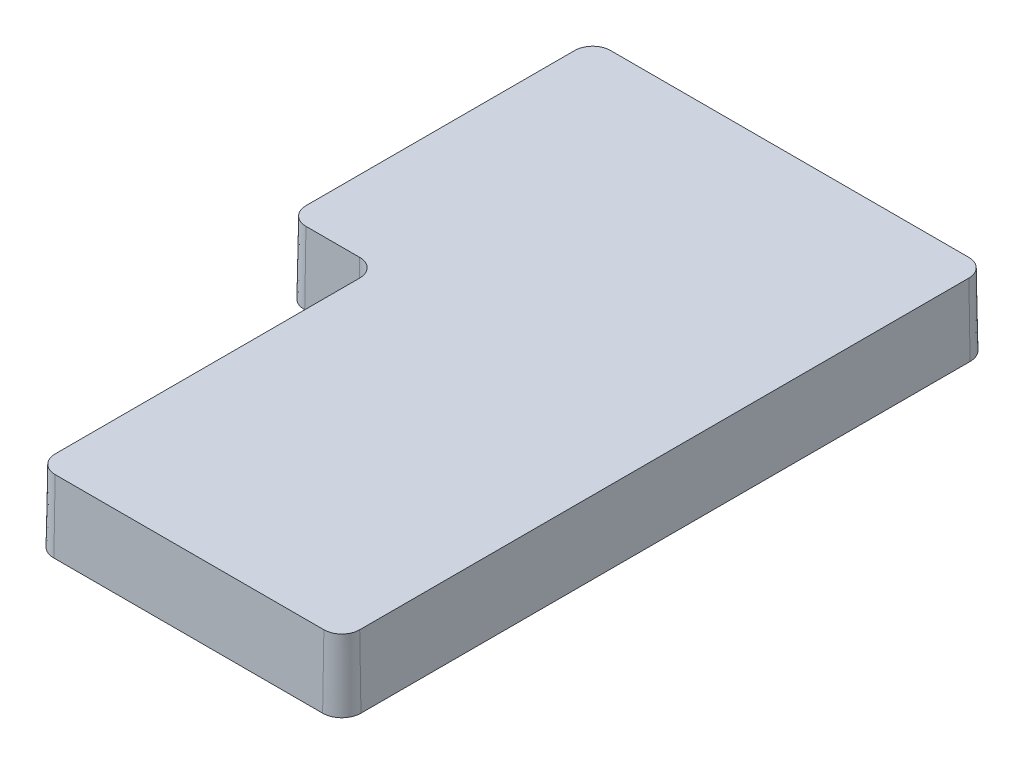
SolidWorks part; units mm, degrees
ref_plane "Front Plane" through (0, 0, 0) normal (0, 0, 1) x (1, 0, 0)
ref_plane "Top Plane" through (0, 0, 0) normal (0, 1, 0) x (1, 0, 0)
ref_plane "Right Plane" through (0, 0, 0) normal (1, 0, 0) x (0, 0, -1)
ref_plane "Right_New_Plane" through (-0.69, 0, 0) normal (1, 0, 0) x (0, 0, -1)
sketch "Sketch1" plane through (0, 0, 0) normal (0, 1, 0) x (1, 0, 0)
  line L0 (9.3071, 15.4536) -> (-10.6929, 15.4536)
  line L1 (10.3071, -19.5464) -> (10.3071, 14.4536)
  line L2 (-5.6929, -20.5464) -> (9.3071, -20.5464)
  line L3 (-6.6929, -2.5464) -> (-6.6929, -19.5464)
  line L4 (-10.6929, -1.5464) -> (-7.6929, -1.5464)
  line L5 (-11.6929, 14.4536) -> (-11.6929, -0.5464)
  line L6 (-55, 0) -> (55, 0) construction
  line L7 (0, -55) -> (0, 55) construction
  line L8 (-0.6929, 15.4536) -> (-0.69, -20.5464) construction
  line L9 (-0.69, -55) -> (-0.69, 55) construction
  line L10 (10.3071, -2.5464) -> (-6.6929, -2.5464) construction
  arc A0 (-10.6929, 15.4536) -> (-11.6929, 14.4536) centre (-10.6929, 14.4536) ccw
  arc A1 (10.3071, 14.4536) -> (9.3071, 15.4536) centre (9.3071, 14.4536) ccw
  arc A2 (9.3071, -20.5464) -> (10.3071, -19.5464) centre (9.3071, -19.5464) ccw
  arc A3 (-6.6929, -19.5464) -> (-5.6929, -20.5464) centre (-5.6929, -19.5464) ccw
  arc A4 (-6.6929, -2.5464) -> (-7.6929, -1.5464) centre (-7.6929, -2.5464) ccw
  arc A5 (-11.6929, -0.5464) -> (-10.6929, -1.5464) centre (-10.6929, -0.5464) ccw
  dimension "D1" = 15.4536
  dimension "D2" = 36
  dimension "D3" = 22
  dimension "D4" = 10.3071
  dimension "D5" = 15
extrude "Boss-Extrude1" add sketch "Sketch1" against normal blind 4 draft 1 draft outward yes
shell "Shell1" thickness 0.5 removed face at (-2.7069, -4, 2.2271)
sketch "Sketch2" plane through (0, -0.5, 0) normal (0, -1, 0) x (-1, 0, 0)
  circle A16 centre (-4.5829, 9.4972) radius 3
  circle A17 centre (7.287, 9.4972) radius 3
  circle A18 centre (-4.5829, -14.3394) radius 3
  circle A19 centre (2.6359, -14.3394) radius 3
extrude "Boss-Extrude2" add sketch "Sketch2" along normal blind 4 draft 1.5
ref_plane "Plane2" through (0, 0, 2.5464) normal (0, 0, 1) x (1, 0, 0)
